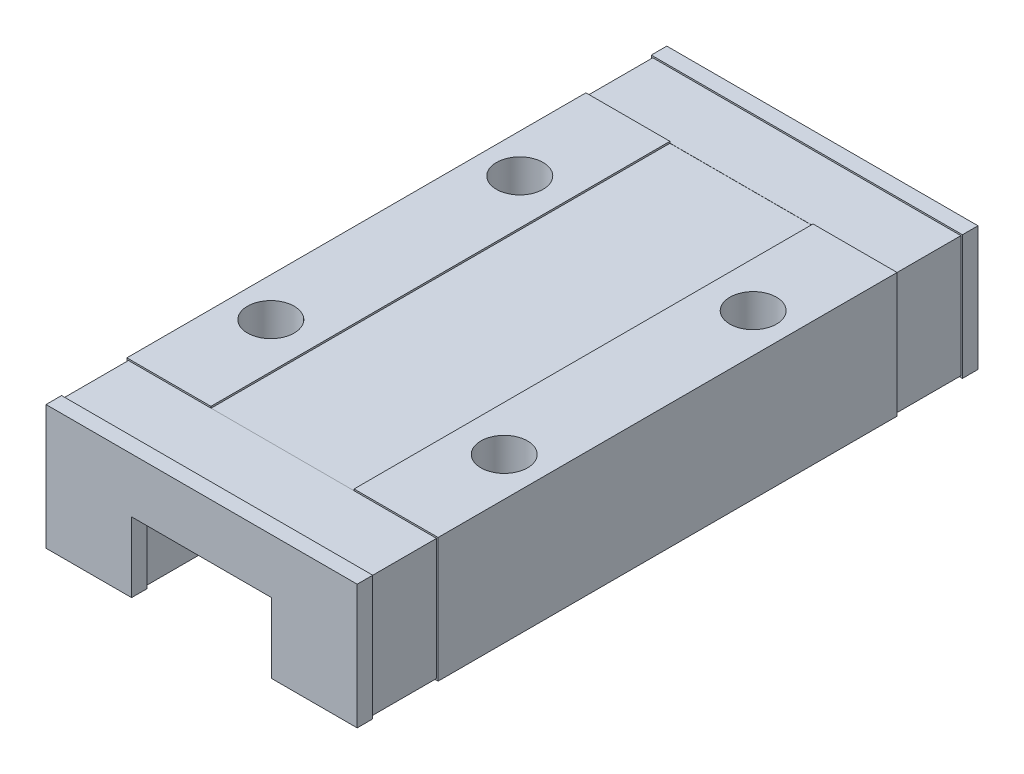
SolidWorks part; units mm, degrees
ref_plane "Front Plane" through (0, 0, 0) normal (0, 0, 1) x (1, 0, 0)
ref_plane "Top Plane" through (0, 0, 0) normal (0, 1, 0) x (1, 0, 0)
ref_plane "Right Plane" through (0, 0, 0) normal (1, 0, 0) x (0, 0, -1)
sketch "Sketch1" plane through (0, 0, 0) normal (0, 0, 1) x (1, 0, 0)
  line L0 (0, 0) -> (0, 14.1385) construction
  line L1 (4.5, 4.5) -> (-4.5, 4.5)
  line L2 (-4.5, 4.5) -> (-4.5, 0)
  line L3 (-4.5, 0) -> (-10, 0)
  line L4 (-10, 0) -> (-10, 8)
  line L5 (-10, 8) -> (10, 8)
  line L6 (10, 0) -> (10, 8)
  line L7 (4.5, 0) -> (10, 0)
  line L8 (4.5, 4.5) -> (4.5, 0)
  point P10 (0, 8)
  point P13 (0, 4.5)
  dimension "D1" = 10
  dimension "D2" = 8
  dimension "D3" = 5.5
  dimension "D4" = 3.5
extrude "Boss-Extrude1" add sketch "Sketch1" along normal blind 39.9 contours L5 L6 L7 L8 L1 L2 L3 L4
sketch "Sketch2" plane through (0, 8, 0) normal (0, 1, 0) x (1, 0, 0)
  line L0 (-10, -19.95) -> (0, -19.95) construction
  line L1 (-10, -39.9) -> (-10, 0) construction
  line L2 (0, -19.95) -> (0, 0) construction
  line L3 (-7.5, -19.95) -> (-7.5, -11.95) construction
  line L4 (-7.5, -11.95) -> (0, -11.95) construction
  circle A0 centre (-7.5, -11.95) radius 1.5
  circle A1 centre (7.5, -11.95) radius 1.5
  circle A2 centre (7.5, -27.95) radius 1.5
  circle A3 centre (-7.5, -27.95) radius 1.5
  dimension "D3" = 3
  dimension "D1" = 7.5
  dimension "D2" = 8
extrude "Cut-Extrude1" cut sketch "Sketch2" against normal blind 4
sketch "Sketch3" plane through (0, 0, 0) normal (0, 0, -1) x (-1, 0, 0)
  line L0 (9.9, 0.1) -> (9.9, 7.9)
  line L1 (9.9, 7.9) -> (-9.9, 7.9)
  line L2 (-9.9, 7.9) -> (-9.9, 0.1)
  line L3 (-9.9, 0.1) -> (-4.6, 0.1)
  line L4 (-4.6, 0.1) -> (-4.6, 4.6)
  line L5 (-4.6, 4.6) -> (4.6, 4.6)
  line L6 (4.6, 4.6) -> (4.6, 0.1)
  line L7 (4.6, 0.1) -> (9.9, 0.1)
  line L8 (10, 0) -> (10, 8)
  line L9 (10, 8) -> (-10, 8)
  line L10 (-10, 8) -> (-10, 0)
  line L11 (-10, 0) -> (-4.5, 0)
  line L12 (-4.5, 0) -> (-4.5, 4.5)
  line L13 (-4.5, 4.5) -> (4.5, 4.5)
  line L14 (4.5, 4.5) -> (4.5, 0)
  line L15 (4.5, 0) -> (10, 0)
  line L16 (10, 0) -> (10, 8)
  line L17 (10, 8) -> (-10, 8)
  line L18 (-10, 8) -> (-10, 0)
  line L19 (-10, 0) -> (-4.5, 0)
  line L20 (-4.5, 0) -> (-4.5, 4.5)
  line L21 (-4.5, 4.5) -> (4.5, 4.5)
  line L22 (4.5, 4.5) -> (4.5, 0)
  line L23 (4.5, 0) -> (10, 0)
  line M17 (10, 0) -> (10, 8)
  line M18 (10, 8) -> (-10, 8)
  line M19 (-10, 8) -> (-10, 0)
  line M20 (-10, 0) -> (-4.5, 0)
  line M21 (-4.5, 0) -> (-4.5, 4.5)
  line M22 (-4.5, 4.5) -> (4.5, 4.5)
  line M23 (4.5, 4.5) -> (4.5, 0)
  line M24 (4.5, 0) -> (10, 0)
  dimension "D1" = 0
  dimension "D2" = 0.1
extrude "Cut-Extrude2" cut sketch "Sketch3" against normal blind 5.2 contours L7 L6 L5 L4 L3 L2 L1 L0 M24 M17 M18 M19 M20 M21 M22 M23 region at (-7.25, 0.0215, 0)
extrude "Cut-Extrude3" cut sketch "Sketch3<3>" along normal blind 5.2 from surface starting at face at (0, 3.125, 39.9)
sketch "Sketch3<3>" plane through (0, 0, 0) normal (0, 0, -1) x (-1, 0, 0) same geometry as "Sketch3"
sketch "Sketch4" plane through (0, 0, 0) normal (0, 0, -1) x (-1, 0, 0)
  line L16 (4.5, 4.5) -> (4.5, 0)
  line L17 (4.5, 0) -> (10, 0)
  line L18 (10, 0) -> (10, 8)
  line L19 (10, 8) -> (-10, 8)
  line L20 (-10, 8) -> (-10, 0)
  line L21 (-10, 0) -> (-4.5, 0)
  line L22 (-4.5, 0) -> (-4.5, 4.5)
  line L23 (-4.5, 4.5) -> (4.5, 4.5)
  line L24 (4.5, 4.5) -> (4.5, 0)
  line L25 (4.5, 0) -> (10, 0)
  line L26 (10, 0) -> (10, 8)
  line L27 (10, 8) -> (-10, 8)
  line L28 (-10, 8) -> (-10, 0)
  line L29 (-10, 0) -> (-4.5, 0)
  line L30 (-4.5, 0) -> (-4.5, 4.5)
  line L31 (-4.5, 4.5) -> (4.5, 4.5)
  dimension "D1" = 0.1
extrude "Boss-Extrude2" add sketch "Sketch4" against normal blind 1
extrude "Boss-Extrude3" add sketch "Sketch4<2>" along normal blind 1 from surface starting at face at (0, 3.175, 39.9)
sketch "Sketch4<2>" plane through (0, 0, 0) normal (0, 0, -1) x (-1, 0, 0) same geometry as "Sketch4"
sketch "Sketch5" plane through (0, 8, 0) normal (0, 1, 0) x (1, 0, 0)
  line L0 (0, -5.2) -> (0, -34.7) construction
  line L1 (-9.9, -5.2) -> (9.9, -5.2) construction
  line L2 (-9.9, -34.7) -> (9.9, -34.7) construction
  line L3 (-4.6, -5.2) -> (-4.6, -34.7)
  line L4 (-10, -5.2) -> (10, -5.2) construction
  line L5 (-10, -34.7) -> (10, -34.7) construction
  line L6 (-4.6, -34.7) -> (4.6, -34.7)
  line L7 (-4.6, -5.2) -> (4.6, -5.2)
  line L8 (-10, -34.7) -> (-10, -5.2) construction
  line L9 (4.6, -5.2) -> (4.6, -34.7)
  dimension "D1" = 5.4
extrude "Cut-Extrude4" cut sketch "Sketch5" against normal blind 0.11
